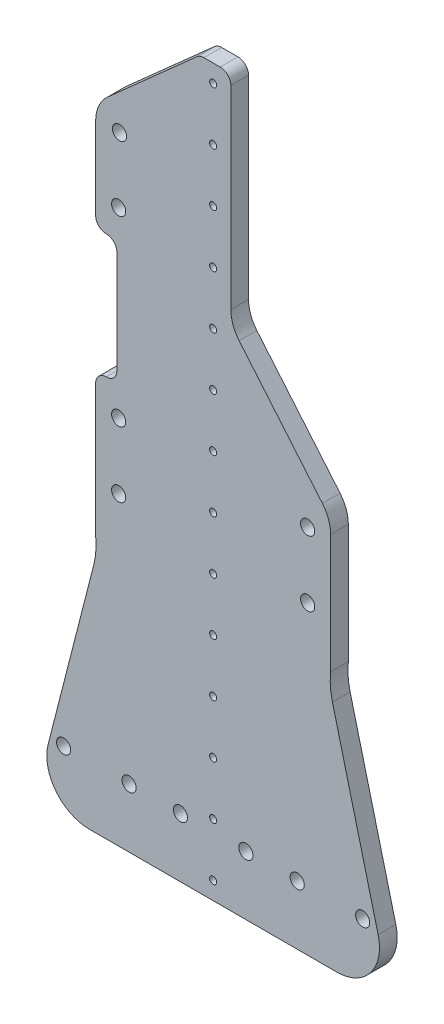
SolidWorks part; units mm, degrees
material "Thornel Mat VMA"
ref_plane "前视基准面" through (0, 0, 0) normal (0, 0, 1) x (1, 0, 0)
ref_plane "上视基准面" through (0, 0, 0) normal (0, 1, 0) x (1, 0, 0)
ref_plane "右视基准面" through (0, 0, 0) normal (1, 0, 0) x (0, 0, -1)
sketch "草图1" plane through (0, 0, 0) normal (0, 0, 1) x (1, 0, 0)
  line L0 (-33.7003, -37.0459) -> (-46.625, -87.5234)
  line L1 (-2.5975, 102.5) -> (2, 102.5)
  line L3 (-5, -102.5) -> (5, -102.5)
  line L4 (5, 99.5) -> (5, 41.0013)
  line L5 (-35, -102.5) -> (-5, -102.5)
  line L6 (0, -55) -> (0, 55) construction
  line L7 (35, -102.5) -> (5, -102.5)
  line L9 (33.2, 7.3649) -> (33.2, -29.8545)
  line L12 (5, 41.0013) -> (33.2, 7.3649)
  line L14 (33.7003, -37.0459) -> (46.625, -87.5234)
  line L15 (-33.2, -29.8545) -> (-33.2, 76.25)
  line L16 (-33.2, 76.25) -> (-4.5933, 101.7398)
  arc A0 (-35, -102.5) -> (-46.625, -87.5234) centre (-35, -90.5) cw
  arc A3 (35, -102.5) -> (46.625, -87.5234) centre (35, -90.5) ccw
  circle A4 centre (-9.25, -85.8) radius 2
  circle A5 centre (9.25, -85.8) radius 2
  circle A6 centre (23.75, -85.8) radius 2
  circle A7 centre (42.25, -85.8) radius 2
  circle A8 centre (-42.25, -85.8) radius 2
  circle A9 centre (-23.75, -85.8) radius 2
  arc A10 (2, 102.5) -> (5, 99.5) centre (2, 99.5) cw
  arc A11 (-2.5975, 102.5) -> (-4.5933, 101.7398) centre (-2.5975, 99.5) ccw
  arc A12 (-33.7003, -37.0459) -> (-33.2, -29.8545) centre (-53.0752, -32.085) ccw
  arc A15 (33.7003, -37.0459) -> (33.2, -29.8545) centre (53.0752, -32.085) cw
  point P36 (5, 102.5)
  point P39 (-5, 102.5)
  circle B0 centre (-26.7, 2.25) radius 2
  circle B1 centre (-26.7, -16.25) radius 2
  circle B2 centre (-26.4562, 72.25) radius 2
  circle B3 centre (-26.7, 53.7516) radius 2
  circle B4 centre (26.7, 2.25) radius 2
  circle B5 centre (26.7, -16.25) radius 2
  dimension "D5" = 12
  dimension "D10" = 4
  dimension "D11" = 174.75
  dimension "D12" = 4
  dimension "D17" = 3
  dimension "D18" = 20
  dimension "D19" = 6.5
  dimension "D22" = 70.415
  dimension "D1" = 30
  dimension "D2" = 5
  dimension "D3" = 102.5
  dimension "D4" = 205
  dimension "D6" = 5
  dimension "D7" = 10
  dimension "D8" = 9.25
  dimension "D9" = 16.7
  dimension "D13" = 18.5
  dimension "D14" = 18.5
  dimension "D15" = 14.5
  dimension "D16" = 14.5
  dimension "D21" = 26.7
  dimension "D23" = 104.75
  dimension "D24" = 65.4541
  dimension "D25" = 4
sketch_block_instance "块1-1"
sketch_block "块1" parameters "D1"=4, "D2"=4, "D3"=18.5
sketch_block_instance "块1-2"
sketch_block_instance "块1-3"
sketch "草图2" plane through (0, 0, 0) normal (0, 0, 1) x (1, 0, 0)
  line L0 (-2.5975, 102.5) -> (2, 102.5) construction
  circle A0 centre (0, 97.5) radius 1
  dimension "D1" = 2
  dimension "D2" = 5
extrude "凸台-拉伸1" add sketch "草图1" along normal blind 5 contours L7 A3 L0 A0 L5 L3 A4 A5 | L4 L1 | L0 | A15 L12 region at (-2.9125, -21.1539, 0)
extrude "切除-拉伸1" cut sketch "草图2" along normal blind 20
pattern_linear "阵列(线性)1" count 14 spacing 15 along (0, -1, 0) of "切除-拉伸1"
fillet "圆角1" radius 10 3 edges at (33.2, 7.3649, 2.5) (5, 41.0013, 2.5) (-33.2, 76.25, 2.5)
sketch "草图3" plane through (0, 0, 0) normal (0, 0, 1) x (1, 0, 0)
  line L0 (-33.2, -29.8545) -> (-33.2, 71.7666) construction
  line L1 (-33.2, 45.5693) -> (-27.2, 45.5693)
  line L2 (-33.2, 45.5693) -> (-33.2, 10.5693)
  line L3 (-33.2, 10.5693) -> (-27.2, 10.5693)
  line L4 (-27.2, 45.5693) -> (-27.2, 10.5693)
  dimension "D1" = 6
  dimension "D2" = 35
extrude "切除-拉伸2" cut sketch "草图3" along normal blind 13
fillet "圆角2" radius 3 4 edges at (-33.2, 45.5693, 2.5) (-27.2, 45.5693, 2.5) (-33.2, 10.5693, 2.5) (-27.2, 10.5693, 2.5)
